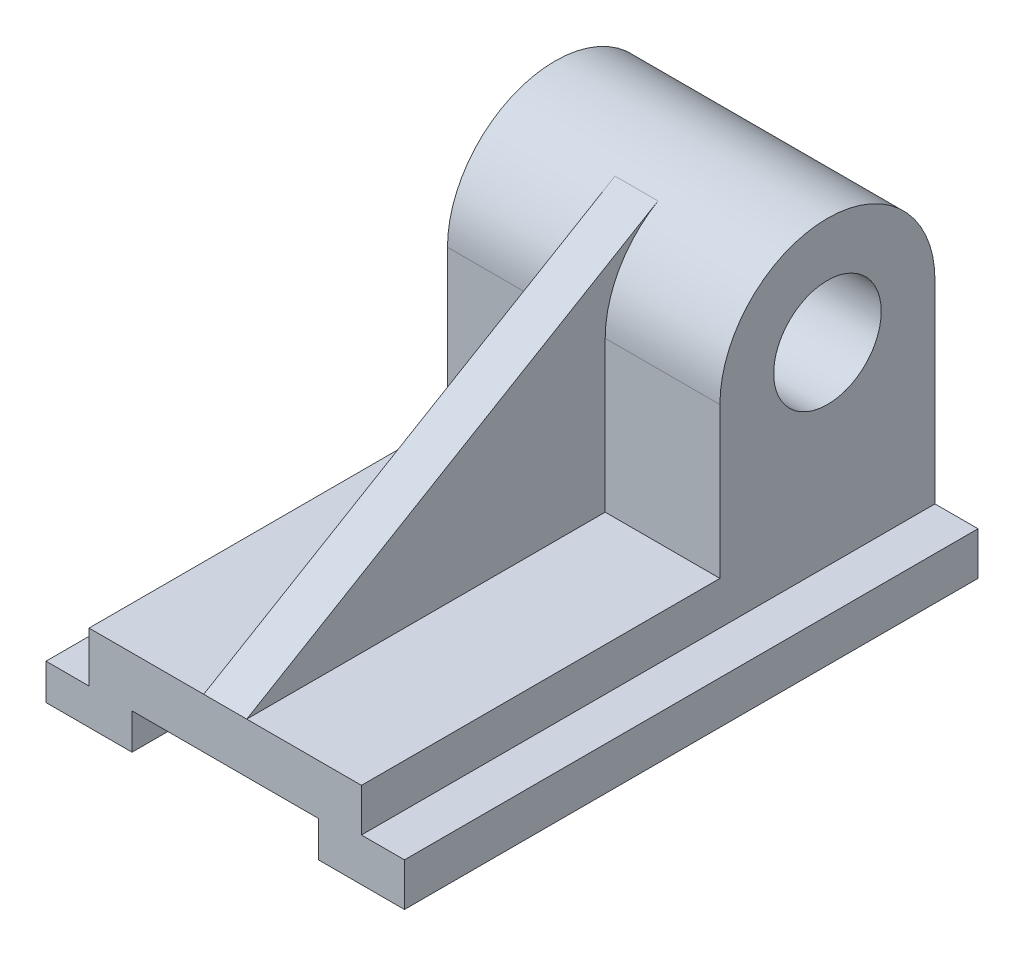
SolidWorks part; units mm, degrees
ref_plane "Front Plane" through (0, 0, 0) normal (0, 0, 1) x (1, 0, 0)
ref_plane "Top Plane" through (0, 0, 0) normal (0, 1, 0) x (1, 0, 0)
ref_plane "Right Plane" through (0, 0, 0) normal (1, 0, 0) x (0, 0, -1)
sketch "Sketch1" plane through (0, 0, 0) normal (0, 0, 1) x (1, 0, 0)
  line L0 (26, 0) -> (-26, 0)
  line L1 (-26, 0) -> (-26, -10)
  line L2 (-26, -10) -> (-50, -10)
  line L3 (-50, -10) -> (-50, 0)
  line L4 (-50, 0) -> (-38, 0)
  line L5 (-38, 0) -> (-38, 14)
  line L6 (-38, 14) -> (38, 14)
  line L7 (38, 14) -> (38, 2)
  line L8 (38, 2) -> (50, 2)
  line L9 (50, 2) -> (50, -10)
  line L10 (50, -10) -> (26, -10)
  line L11 (26, -10) -> (26, 0)
  point P4 (0, 0)
  dimension "D1" = 52
  dimension "D2" = 10
  dimension "D3" = 24
  dimension "D4" = 10
  dimension "D5" = 24
  dimension "D6" = 12
  dimension "D7" = 12
  dimension "D8" = 12
  dimension "D9" = 76
  dimension "D10" = 10
extrude "Boss-Extrude1" add sketch "Sketch1" along normal blind 160
sketch "Sketch2" plane through (50, 0, 0) normal (1, 0, 0) x (0, 0, -1)
  line L0 (-160, 14) -> (0, 14) construction
  line L1 (0, 14) -> (-60, 14)
  line L2 (0, 14) -> (0, 86)
  line L3 (0, 86) -> (-60, 86)
  line L4 (-60, 14) -> (-60, 86)
  point P4 (0, 0)
  point P5 (0, 0)
  dimension "D1" = 72
  dimension "D2" = 60
extrude "Boss-Extrude2" add sketch "Sketch2" against normal blind 76 from offset 12 contours L2 L3 L4 L1 offset against normal yes
fillet "Fillet1" 2 edges at (0, 86, 0) (0, 86, 60) type full round first side face at (0, 11.3333, 0) second side face at (0, 50, 60) middle face at (0, 86, 30)
sketch "Sketch3" plane through (38, 0, 0) normal (1, 0, 0) x (0, 0, -1)
  line L0 (-30, 56) -> (-30, 86) construction
  circle A0 centre (-30, 56) radius 15
  arc A1 (0, 56) -> (-60, 56) centre (-30, 56) ccw construction
  dimension "D1" = 30
extrude "Cut-Extrude1" cut sketch "Sketch3" against normal blind 76
sketch "Sketch4" plane through (0, 0, 0) normal (1, 0, 0) x (0, 0, -1)
  line L0 (-45.2665, 81.825) -> (-160, 14)
  arc A0 (0, 56) -> (-60, 56) centre (-30, 56) ccw construction
rib "Rib1" sketch "Sketch4" sketch "Sketch4" thickness 12 extrusion direction parallel to sketch draft on no parameters "D1"=12
